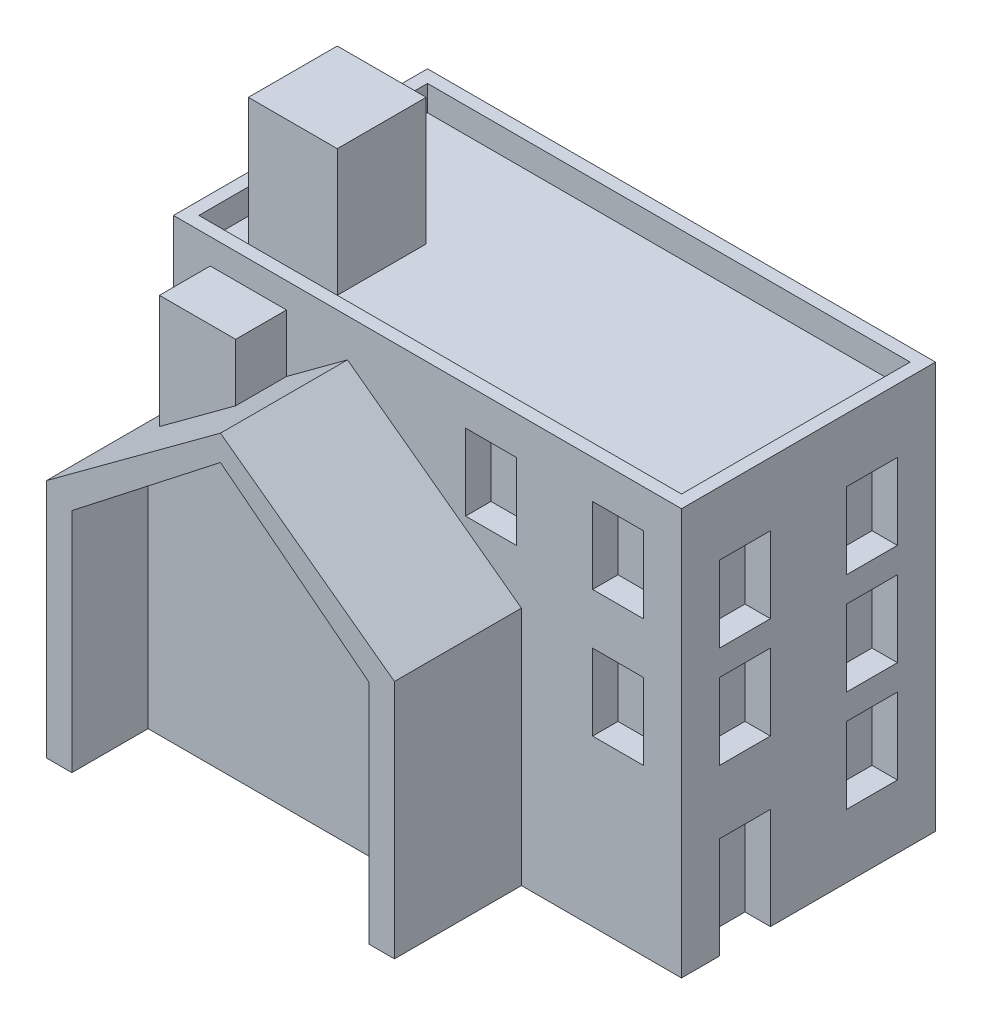
SolidWorks part; units mm, degrees
note: The reader was unsure of these and kept them because the rebuilt part matched: shared geometry of "Croquis4<3>".
ref_plane "Alzado" through (0, 0, 0) normal (0, 0, 1) x (1, 0, 0)
ref_plane "Planta" through (0, 0, 0) normal (0, 1, 0) x (1, 0, 0)
ref_plane "Vista lateral" through (0, 0, 0) normal (1, 0, 0) x (0, 0, -1)
sketch "Croquis1" plane through (0, 0, 0) normal (0, 1, 0) x (1, 0, 0)
  line L1 (-10, -5) -> (10, -5)
  line L2 (-10, -5) -> (-10, 5)
  line L3 (-10, 5) -> (10, 5)
  line L4 (10, -5) -> (10, 5)
  line L5 (-10, -5) -> (10, 5) construction
  line L6 (-10, 5) -> (10, -5) construction
  point P0 (0, 0)
  dimension "D1" = 20
  dimension "D2" = 10
extrude "Saliente-Extruir1" add sketch "Croquis1" along normal blind 15
sketch "Croquis2" plane through (0, 0, 5) normal (0, 0, 1) x (1, 0, 0)
  line L0 (-10, 0) -> (3.6989, 0)
  line L1 (-10, 0) -> (10, 0) construction
  line L2 (3.6989, 0) -> (3.6989, 9.4601)
  line L4 (-10, 15) -> (-10, 0) construction
  line L5 (-10, 9.4601) -> (-10, 0)
  line L6 (-10, 9.4601) -> (-3.1506, 14.5)
  line L7 (-3.1506, 14.5) -> (3.6989, 9.4601)
  line L8 (-3.1506, 0) -> (-3.1506, 15) construction
  line L9 (-10, 15) -> (10, 15) construction
  point P5 (-3.1506, 12.3768)
  dimension "D1" = 0.5
extrude "Saliente-Extruir2" add sketch "Croquis2" along normal blind 5
sketch "Croquis3" plane through (0, 0, 5) normal (0, 0, 1) x (1, 0, 0)
  line L0 (-8.5522, 10.5254) -> (-8.5522, 15)
  line L1 (-3.1506, 14.5) -> (-10, 9.4601) construction
  line L2 (-10, 15) -> (10, 15) construction
  line L3 (-8.5522, 15) -> (-5.5522, 15)
  line L4 (-5.5522, 15) -> (-5.5522, 12.7328)
  line L12 (-10, 9.4601) -> (-3.1506, 14.5)
  line L13 (-3.1506, 14.5) -> (3.6989, 9.4601)
  line L14 (3.6989, 9.4601) -> (3.6989, 0)
  line L15 (3.6989, 0) -> (10, 0)
  line L16 (10, 0) -> (10, 15)
  line L17 (10, 15) -> (-10, 15)
  line L18 (-10, 15) -> (-10, 9.4601)
  line L19 (-8.5522, 10.5254) -> (-5.5522, 12.7328)
  dimension "D1" = 3
  dimension "D2" = 0
extrude "Saliente-Extruir3" add sketch "Croquis3" along normal blind 2
sketch "Croquis4" plane through (0, 15, 0) normal (0, 1, 0) x (1, 0, 0)
  line L0 (-10, -4.5) -> (-10, -5)
  line L1 (-10, 4.5) -> (-9.982, 4.5)
  line L2 (-10, 4.5) -> (-10, -4.5)
  line L3 (-9.5, -4.5) -> (9.5, -4.5)
  line L4 (10, 4.5) -> (10, -4.5)
  line L5 (-10, 4.5) -> (10, -4.5) construction
  line L6 (-10, -4.5) -> (10, 4.5) construction
  line L7 (-9.5, 5) -> (9.5, 5)
  line L8 (-9.5, 5) -> (-9.5, 4.982)
  line L9 (-9.5, -5) -> (9.5, -5)
  line L10 (9.5, 4.5) -> (9.5, -4.5)
  line L11 (-9.5, 5) -> (9.5, -5) construction
  line L12 (-9.5, -5) -> (9.5, 5) construction
  line L13 (-10, -5) -> (-9.5, -5)
  line L14 (-9.5, 5) -> (-10, 5)
  line L15 (-10, 5) -> (-10, 4.5)
  line L16 (9.5, 5) -> (10, 5)
  line L17 (10, 5) -> (10, 4.5)
  line L18 (10, -4.5) -> (10, -5)
  line L19 (10, -5) -> (9.5, -5)
  line L20 (-9.5, 4.5) -> (9.5, 4.5)
  line L21 (-9.5, 4.5) -> (-9.5, -4.5)
  line L22 (-8.5522, -5) -> (-8.5522, -3.5) construction
  line L23 (-10, -3.5) -> (-8.5522, -3.5) construction
  line L29 (-8.5522, -3.5) -> (-5.0522, -3.5)
  line L30 (-8.5522, -3.5) -> (-8.5522, 0)
  line L31 (-8.5522, 0) -> (-5.0522, 0)
  line L32 (-5.0522, -3.5) -> (-5.0522, 0)
  circle A4 centre (-10, 5) radius 0.5003 construction
  circle A5 centre (-10, 5) radius 1.5 construction
  circle A6 centre (-10, -5) radius 0.5 construction
  circle A7 centre (-10, -5) radius 1.5 construction
  circle A8 centre (10, -5) radius 0.5 construction
  circle A9 centre (10, -5) radius 1.5 construction
  circle A10 centre (10, 5) radius 0.5 construction
  circle A11 centre (10, 5) radius 1.5 construction
  point P2 (0, 0)
  point P22 (0, 0)
  dimension "D1" = 1.0006
  dimension "D2" = 3
  dimension "D3" = 3
  dimension "D4" = 1
  dimension "D5" = 1
  dimension "D6" = 3
  dimension "D7" = 1
  dimension "D8" = 3
  dimension "D9" = 19
  dimension "D10" = 3.5
  dimension "D11" = 3.5
extrude "Saliente-Extruir4" add sketch "Croquis4" along normal blind 1
extrude "Saliente-Extruir5" add sketch "Croquis4<3>" along normal blind 5 contours L29 L32 L31 L30
sketch "Croquis4<3>" plane through (0, 15, 0) normal (0, 1, 0) x (1, 0, 0) same geometry as "Croquis4"
sketch "Croquis5" plane through (0, 0, 0) normal (0, -1, 0) x (1, 0, 0)
  circle A0 centre (0, 0) radius 1.575
  dimension "D1" = 3.15
extrude "Cortar-Extruir1" cut sketch "Croquis5" against normal blind 2.5
sketch "Croquis6" plane through (0, 0, 10) normal (0, 0, 1) x (1, 0, 0)
  line L0 (-3.1506, 14.5) -> (-3.1506, 0) construction
  line L1 (-10, 9.4601) -> (3.6989, 9.4601) construction
  line L2 (-10, 9.4601) -> (-9, 9.4601) construction
  line L3 (-3.1506, 14.5) -> (-3.1506, 13.5) construction
  line L4 (3.6989, 9.4601) -> (2.6989, 9.4601) construction
  line L5 (-10, 9.4601) -> (-10, 0)
  line L6 (-10, 0) -> (3.6989, 0)
  line L7 (3.6989, 0) -> (3.6989, 9.4601)
  line L8 (3.6989, 9.4601) -> (-3.1506, 14.5)
  line L9 (-3.1506, 14.5) -> (-10, 9.4601)
  line L10 (-10, 9.4601) -> (-10, 0)
  line L11 (-10, 0) -> (3.6989, 0)
  line L12 (3.6989, 0) -> (3.6989, 9.4601)
  line L13 (3.6989, 9.4601) -> (-3.1506, 14.5)
  line L14 (-3.1506, 14.5) -> (-10, 9.4601)
  line L15 (-9, 0) -> (-9, 8.9357)
  line L16 (3.6989, 9.4601) -> (3.1062, 8.6546) construction
  line L17 (-3.1506, 13.5) -> (-9, 8.9357)
  line L18 (2.6989, 8.9336) -> (2.6989, 0)
  line L19 (-10, 9.4601) -> (-9.4073, 8.6546) construction
  line L20 (-3.1506, 13.5) -> (2.6989, 8.9336)
  dimension "D2" = 1
  dimension "D3" = 1
  dimension "D4" = 1
  dimension "D5" = 1
  dimension "D6" = 1
  dimension "D1" = 0
extrude "Cortar-Extruir2" cut sketch "Croquis6" against normal blind 3
sketch "Croquis7" plane through (0, 0, 5) normal (0, 0, 1) x (1, 0, 0)
  line L0 (0, 16) -> (0, 0) construction
  line L1 (-10, 16) -> (10, 16) construction
  line L2 (0, 0) -> (10, 0) construction
  line L3 (-1.1095, 12.9981) -> (13.6901, 12.9981) construction
  line L4 (1.5, 14.4981) -> (3.5, 14.4981)
  line L5 (1.5, 14.4981) -> (1.5, 11.4981)
  line L6 (1.5, 11.4981) -> (3.5, 11.4981)
  line L7 (3.5, 14.4981) -> (3.5, 11.4981)
  line L8 (1.5, 14.4981) -> (3.5, 11.4981) construction
  line L9 (1.5, 11.4981) -> (3.5, 14.4981) construction
  line L10 (6.5, 14.4981) -> (8.5, 14.4981)
  line L11 (6.5, 14.4981) -> (6.5, 11.4981)
  line L12 (6.5, 11.4981) -> (8.5, 11.4981)
  line L13 (8.5, 14.4981) -> (8.5, 11.4981)
  line L14 (6.5, 14.4981) -> (8.5, 11.4981) construction
  line L15 (6.5, 11.4981) -> (8.5, 14.4981) construction
  line L16 (6.5, 9.4981) -> (8.5, 9.4981)
  line L17 (6.5, 9.4981) -> (6.5, 6.4981)
  line L18 (6.5, 6.4981) -> (8.5, 6.4981)
  line L19 (8.5, 9.4981) -> (8.5, 6.4981)
  line L20 (6.5, 9.4981) -> (8.5, 6.4981) construction
  line L21 (6.5, 6.4981) -> (8.5, 9.4981) construction
  line L22 (3.6989, 9.4601) -> (-3.1506, 14.5) construction
  line L23 (10, 8) -> (-12.2116, 8) construction
  line L24 (10, 16) -> (10, 0) construction
  point P5 (2.5, 12.9981)
  point P12 (7.5, 12.9981)
  point P17 (7.5, 7.9981)
  point P30 (2.5737, 12.9981)
  point P31 (7.3653, 12.9981)
  point P32 (7.3653, 8)
  dimension "D1" = 2
  dimension "D2" = 3
  dimension "D3" = 2
  dimension "D4" = 3
  dimension "D5" = 3
  dimension "D6" = 2
  dimension "D7" = 1.5019
  dimension "D8" = 2
  dimension "D9" = 1.5
  dimension "D10" = 1.5
  dimension "D11" = 3
extrude "Cortar-Extruir3" cut sketch "Croquis7" against normal blind 1
sketch "Croquis8" plane through (-10, 0, 0) normal (-1, 0, 0) x (0, 0, 1)
  line L0 (5, 9.4601) -> (5, 0) construction
  line L1 (0, 16) -> (0, 0) construction
  line L2 (-5, 12) -> (5, 12) construction
  line L3 (-5, 8) -> (5, 8) construction
  line L4 (-5, 4) -> (5, 4) construction
  line L5 (-2.5, 4) -> (-2.5, 12) construction
  line L6 (-5, 0) -> (10, 0)
  line L7 (10, 0) -> (10, 9.4601)
  line L8 (10, 9.4601) -> (5, 9.4601)
  line L9 (5, 9.4601) -> (5, 16)
  line L10 (5, 16) -> (-5, 16)
  line L11 (-5, 16) -> (-5, 0)
  line L12 (-5, 0) -> (10, 0) construction
  line L13 (10, 0) -> (10, 9.4601) construction
  line L14 (10, 9.4601) -> (5, 9.4601) construction
  line L15 (5, 9.4601) -> (5, 16) construction
  line L16 (5, 16) -> (-5, 16) construction
  line L17 (-5, 16) -> (-5, 0) construction
  line L18 (2.5, 4) -> (2.5, 12) construction
  line L19 (2.5, 4) -> (2.5, 0) construction
  line L20 (1.5, 0) -> (3.5, 0)
  line L21 (1.5, 0) -> (1.5, 4)
  line L22 (1.5, 4) -> (3.5, 4)
  line L23 (3.5, 0) -> (3.5, 4)
  line L25 (-3.5, 2.5) -> (-1.5, 2.5)
  line L26 (-3.5, 2.5) -> (-3.5, 5.5)
  line L27 (-3.5, 5.5) -> (-1.5, 5.5)
  line L28 (-1.5, 2.5) -> (-1.5, 5.5)
  line L29 (-3.5, 2.5) -> (-1.5, 5.5) construction
  line L30 (-3.5, 5.5) -> (-1.5, 2.5) construction
  line L31 (-3.5, 6.5) -> (-1.5, 6.5)
  line L32 (-3.5, 6.5) -> (-3.5, 9.5)
  line L33 (-3.5, 9.5) -> (-1.5, 9.5)
  line L34 (-1.5, 6.5) -> (-1.5, 9.5)
  line L35 (-3.5, 6.5) -> (-1.5, 9.5) construction
  line L36 (-3.5, 9.5) -> (-1.5, 6.5) construction
  line L37 (-3.5, 10.5) -> (-1.5, 10.5)
  line L38 (-3.5, 10.5) -> (-3.5, 13.5)
  line L39 (-3.5, 13.5) -> (-1.5, 13.5)
  line L40 (-1.5, 10.5) -> (-1.5, 13.5)
  line L41 (-3.5, 10.5) -> (-1.5, 13.5) construction
  line L42 (-3.5, 13.5) -> (-1.5, 10.5) construction
  line L43 (1.5, 10.5) -> (3.5, 10.5)
  line L44 (1.5, 10.5) -> (1.5, 13.5)
  line L45 (1.5, 13.5) -> (3.5, 13.5)
  line L46 (3.5, 10.5) -> (3.5, 13.5)
  line L47 (1.5, 10.5) -> (3.5, 13.5) construction
  line L48 (1.5, 13.5) -> (3.5, 10.5) construction
  line L49 (1.5, 6.5) -> (3.5, 6.5)
  line L50 (1.5, 6.5) -> (1.5, 9.5)
  line L51 (1.5, 9.5) -> (3.5, 9.5)
  line L52 (3.5, 6.5) -> (3.5, 9.5)
  line L53 (1.5, 6.5) -> (3.5, 9.5) construction
  line L54 (1.5, 9.5) -> (3.5, 6.5) construction
  point P8 (-5, 12)
  point P10 (-5, 8)
  point P11 (-5, 4)
  point P19 (-2.5, 4)
  point P20 (0, 4)
  point P21 (2.5, 4)
  point P36 (-2.5, 8)
  point P49 (2.5, 8)
  dimension "D2" = 2
  dimension "D3" = 4
  dimension "D4" = 3
  dimension "D5" = 2
  dimension "D6" = 3
  dimension "D7" = 2
  dimension "D8" = 3
  dimension "D9" = 3
  dimension "D10" = 2
  dimension "D11" = 2
  dimension "D12" = 3
  dimension "D13" = 2
  dimension "D1" = 0
extrude "Cortar-Extruir4" cut sketch "Croquis8" against normal blind 1
sketch "Croquis9" plane through (0, 0, -5) normal (0, 0, -1) x (-1, 0, 0)
  line L0 (-10, 12) -> (10, 12) construction
  line L1 (6.6667, 16) -> (6.6667, 0) construction
  line L2 (-10, 8) -> (10, 8) construction
  line L3 (-10, 4) -> (-6.6667, 4) construction
  line L4 (-10, 0) -> (10, 0)
  line L5 (10, 0) -> (10, 16)
  line L6 (10, 16) -> (-10, 16)
  line L7 (-10, 16) -> (-10, 0)
  line L8 (-10, 0) -> (10, 0) construction
  line L9 (10, 0) -> (10, 16) construction
  line L10 (10, 16) -> (-10, 16) construction
  line L11 (-10, 16) -> (-10, 0) construction
  line L12 (-10, 4) -> (10, 4) construction
  line L13 (3.3333, 16) -> (3.3333, 0) construction
  line L14 (-4.0867, 2.5) -> (-4.0867, 5.5)
  line L15 (0, 16) -> (0, 0) construction
  line L16 (-7.4167, 2.5) -> (-5.9167, 2.5)
  line L17 (-3.3333, 16) -> (-3.3333, 0) construction
  line L18 (-7.4167, 2.5) -> (-7.4167, 5.5)
  line L19 (-6.6667, 16) -> (-6.6667, 0) construction
  line L20 (-7.4167, 5.5) -> (-5.9167, 5.5)
  line L21 (-5.9167, 2.5) -> (-5.9167, 5.5)
  line L22 (-7.4167, 2.5) -> (-5.9167, 5.5) construction
  line L23 (-7.4167, 5.5) -> (-5.9167, 2.5) construction
  line L24 (-4.0867, 2.5) -> (-2.5867, 2.5)
  line L25 (-2.5867, 2.5) -> (-2.5867, 5.5)
  line L26 (-4.0867, 5.5) -> (-2.5867, 5.5)
  line L27 (-0.7567, 2.5) -> (-0.7567, 5.5)
  line L28 (-0.7567, 2.5) -> (0.7433, 2.5)
  line L29 (0.7433, 2.5) -> (0.7433, 5.5)
  line L30 (-0.7567, 5.5) -> (0.7433, 5.5)
  line L31 (2.5733, 2.5) -> (2.5733, 5.5)
  line L32 (2.5733, 2.5) -> (4.0733, 2.5)
  line L33 (4.0733, 2.5) -> (4.0733, 5.5)
  line L34 (2.5733, 5.5) -> (4.0733, 5.5)
  line L35 (5.9033, 2.5) -> (5.9033, 5.5)
  line L36 (5.9033, 2.5) -> (7.4033, 2.5)
  line L37 (7.4033, 2.5) -> (7.4033, 5.5)
  line L38 (5.9033, 5.5) -> (7.4033, 5.5)
  line L39 (-4.0867, 6.5) -> (-4.0867, 9.5)
  line L40 (-4.0867, 6.5) -> (-2.5867, 6.5)
  line L41 (-2.5867, 6.5) -> (-2.5867, 9.5)
  line L42 (-4.0867, 9.5) -> (-2.5867, 9.5)
  line L43 (-0.7567, 6.5) -> (-0.7567, 9.5)
  line L44 (-0.7567, 6.5) -> (0.7433, 6.5)
  line L45 (0.7433, 6.5) -> (0.7433, 9.5)
  line L46 (-0.7567, 9.5) -> (0.7433, 9.5)
  line L47 (2.5733, 6.5) -> (2.5733, 9.5)
  line L48 (2.5733, 6.5) -> (4.0733, 6.5)
  line L49 (4.0733, 6.5) -> (4.0733, 9.5)
  line L50 (2.5733, 9.5) -> (4.0733, 9.5)
  line L51 (5.9033, 6.5) -> (5.9033, 9.5)
  line L52 (5.9033, 6.5) -> (7.4033, 6.5)
  line L53 (7.4033, 6.5) -> (7.4033, 9.5)
  line L54 (5.9033, 9.5) -> (7.4033, 9.5)
  line L55 (-4.0867, 10.5) -> (-4.0867, 13.5)
  line L56 (-4.0867, 10.5) -> (-2.5867, 10.5)
  line L57 (-2.5867, 10.5) -> (-2.5867, 13.5)
  line L58 (-4.0867, 13.5) -> (-2.5867, 13.5)
  line L59 (-0.7567, 10.5) -> (-0.7567, 13.5)
  line L60 (-0.7567, 10.5) -> (0.7433, 10.5)
  line L61 (0.7433, 10.5) -> (0.7433, 13.5)
  line L62 (-0.7567, 13.5) -> (0.7433, 13.5)
  line L63 (2.5733, 10.5) -> (2.5733, 13.5)
  line L64 (2.5733, 10.5) -> (4.0733, 10.5)
  line L65 (4.0733, 10.5) -> (4.0733, 13.5)
  line L66 (2.5733, 13.5) -> (4.0733, 13.5)
  line L67 (5.9033, 10.5) -> (5.9033, 13.5)
  line L68 (5.9033, 10.5) -> (7.4033, 10.5)
  line L69 (7.4033, 10.5) -> (7.4033, 13.5)
  line L70 (5.9033, 13.5) -> (7.4033, 13.5)
  line L71 (-7.4167, 6.5) -> (-7.4167, 9.5)
  line L72 (-7.4167, 6.5) -> (-5.9167, 6.5)
  line L73 (-5.9167, 6.5) -> (-5.9167, 9.5)
  line L74 (-7.4167, 9.5) -> (-5.9167, 9.5)
  line L75 (-7.4167, 10.5) -> (-7.4167, 13.5)
  line L76 (-7.4167, 10.5) -> (-5.9167, 10.5)
  line L77 (-5.9167, 10.5) -> (-5.9167, 13.5)
  line L78 (-7.4167, 13.5) -> (-5.9167, 13.5)
  point P2 (-10, 12)
  point P4 (-10, 8)
  point P6 (-10, 4)
  point P7 (5, 16)
  point P8 (0, 16)
  point P9 (-5, 16)
  point P17 (6.6667, 16)
  point P18 (3.3333, 16)
  point P19 (0, 16)
  point P20 (-3.3333, 16)
  point P21 (-6.6667, 16)
  dimension "D2" = 1.5
  dimension "D3" = 3
  dimension "D1" = 0
  dimension "D4" = 5
  dimension "D5" = 3
extrude "Cortar-Extruir5" cut sketch "Croquis9" against normal blind 1
mirror "Simetría1" about plane through (0, 0, 0) normal (1, 0, 0) of "Cortar-Extruir4"
